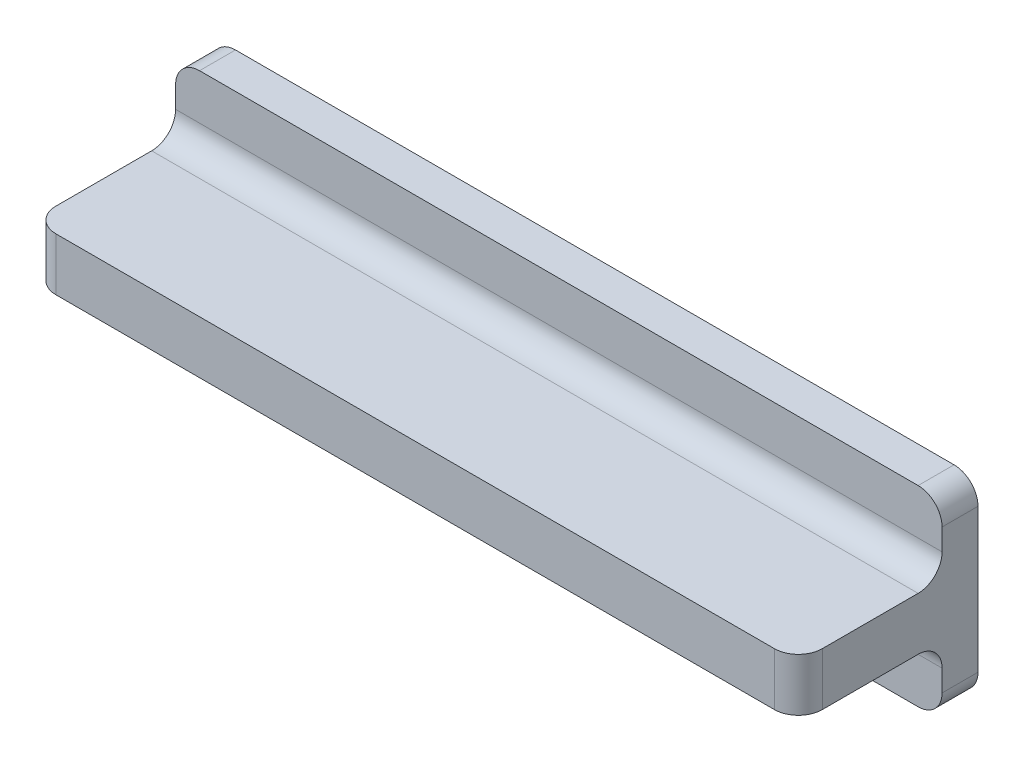
SolidWorks part; units mm, degrees
material "ABS"
ref_plane "X-Y Datum" through (0, 0, 0) normal (0, 0, 1) x (1, 0, 0)
ref_plane "X-Z Datum" through (0, 0, 0) normal (0, 1, 0) x (1, 0, 0)
ref_plane "Y-Z Datum" through (0, 0, 0) normal (1, 0, 0) x (0, 0, -1)
sketch "Sketch1" plane through (0, 0, 0) normal (0, 0, 1) x (1, 0, 0)
  line L1 (-50.8, 12.7) -> (50.8, 12.7)
  line L2 (-50.8, 12.7) -> (-50.8, -12.7)
  line L3 (-50.8, -12.7) -> (50.8, -12.7)
  line L4 (50.8, 12.7) -> (50.8, -12.7)
  line L5 (-50.8, 12.7) -> (50.8, -12.7) construction
  line L6 (-50.8, -12.7) -> (50.8, 12.7) construction
  point P0 (0, 0)
  dimension "D1" = 101.6
  dimension "D2" = 25.4
extrude "Boss-Extrude1" add sketch "Sketch1" along normal blind 4.7625
sketch "Sketch2" plane through (0, 0, 4.7625) normal (0, 0, 1) x (1, 0, 0)
  line L0 (50.8, -12.7) -> (50.8, 12.7) construction
  line L1 (-50.8, 3.5) -> (50.8, 3.5)
  line L2 (-50.8, 3.5) -> (-50.8, -3.5)
  line L3 (-50.8, -3.5) -> (50.8, -3.5)
  line L4 (50.8, 3.5) -> (50.8, -3.5)
  line L5 (-50.8, 3.5) -> (50.8, -3.5) construction
  line L6 (-50.8, -3.5) -> (50.8, 3.5) construction
  point P0 (0, 0)
  dimension "D1" = 7
extrude "Boss-Extrude2" add sketch "Sketch2" along normal blind 19.05
fillet "Fillet1" radius 3.175 8 edges at (0, 3.5, 4.7625) (0, -3.5, 4.7625) (-50.8, 0, 23.8125) (50.8, 0, 23.8125) (50.8, 12.7, 2.3813) (50.8, -12.7, 2.3813) (-50.8, 12.7, 2.3813) (-50.8, -12.7, 2.3813)
